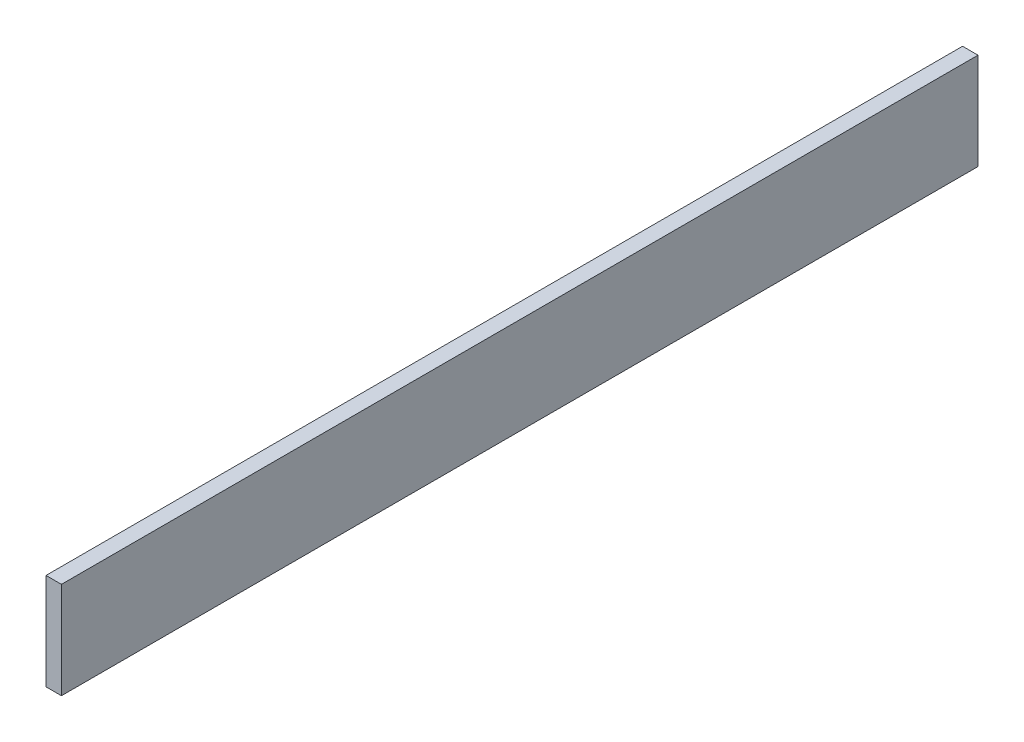
SolidWorks part; units mm, degrees
ref_plane "Front Plane" through (0, 0, 0) normal (0, 0, 1) x (1, 0, 0)
ref_plane "Top Plane" through (0, 0, 0) normal (0, 1, 0) x (1, 0, 0)
ref_plane "Right Plane" through (0, 0, 0) normal (1, 0, 0) x (0, 0, -1)
sketch "Sketch1" plane through (0, 0, 0) normal (1, 0, 0) x (0, 0, -1)
  line L1 (0, 0) -> (190, 0)
  line L2 (0, 0) -> (0, 20)
  line L3 (0, 20) -> (190, 20)
  line L4 (190, 0) -> (190, 20)
  dimension "D1" = 20
  dimension "D2" = 190
extrude "Boss-Extrude1" add sketch "Sketch1" along normal blind 3.2
